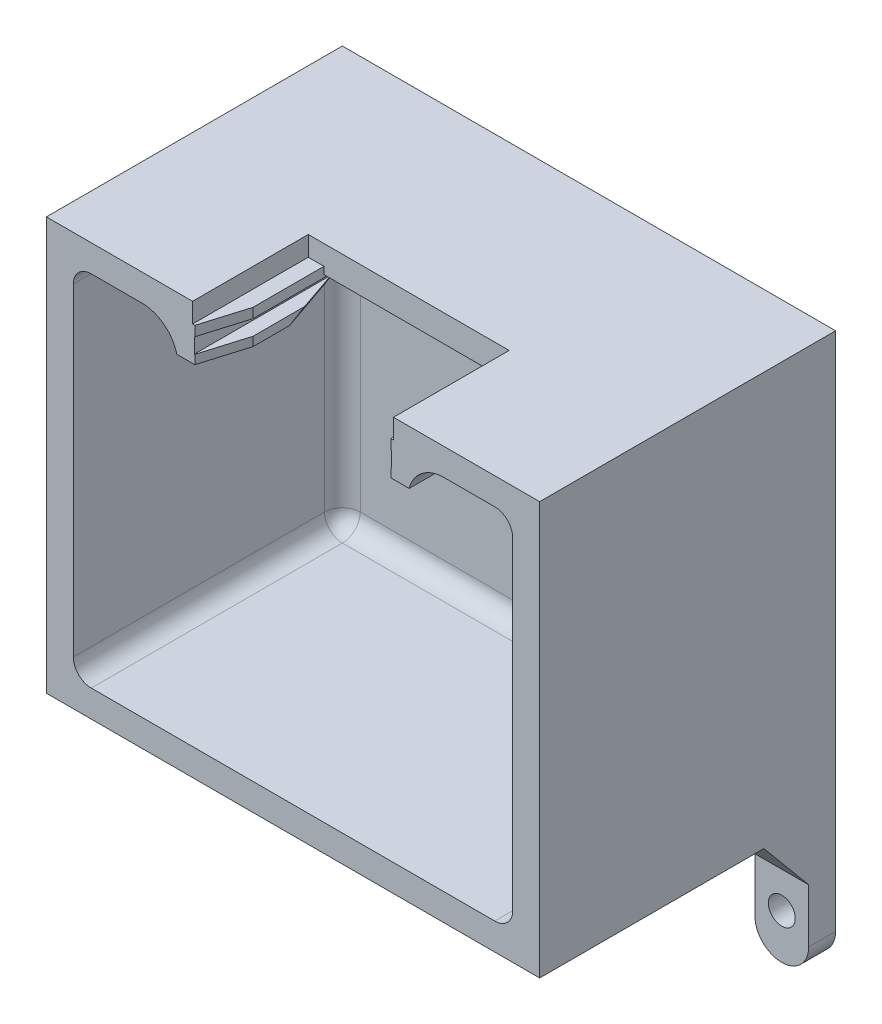
SolidWorks part; units mm, degrees
ref_plane "Front" through (0, 0, 0) normal (0, 0, 1) x (1, 0, 0)
ref_plane "Top" through (0, 0, 0) normal (0, 1, 0) x (1, 0, 0)
ref_plane "Right" through (0, 0, 0) normal (1, 0, 0) x (0, 0, -1)
sketch "Эскиз1" plane through (0, 0, 0) normal (0, 0, 1) x (1, 0, 0)
  line L0 (-27.5, -34) -> (-27.5, 40) construction
  line L1 (27.5, 43) -> (-27.5, 43)
  line L2 (27.5, 43) -> (27.5, -3)
  line L3 (21.5, -3) -> (-21.5, -3)
  line L4 (-27.5, 43) -> (-27.5, -3)
  line L5 (-27.5, 40) -> (27.5, 40) construction
  line L6 (8.25, 40) -> (-8.25, 40)
  line L7 (8.25, 40) -> (8.25, 30)
  line L8 (8.25, 30) -> (-8.25, 30)
  line L9 (-8.25, 40) -> (-8.25, 30)
  line L10 (-27.5, -3) -> (-27.5, -18)
  line L11 (-27.5, -18) -> (-21.5, -18)
  line L12 (-21.5, -42) -> (-21.5, -6) construction
  line L13 (-21.5, -18) -> (-21.5, -3)
  line L14 (27.5, -3) -> (27.5, -18)
  line L15 (27.5, -18) -> (21.5, -18)
  line L16 (21.5, -42) -> (21.5, -6) construction
  line L17 (21.5, -18) -> (21.5, -3)
  circle A0 centre (-24.5, -13) radius 1.5
  circle A1 centre (24.5, -13) radius 1.5
  point P13 (0, 30)
  point P33 (-24.5, -18)
  point P34 (24.5, -18)
  dimension "D4" = 3
  dimension "D1" = 16.5
  dimension "D2" = 10
  dimension "D3" = 15
  dimension "D5" = 5
  dimension "D6" = 46
extrude "Бобышка-Вытянуть1" add sketch "Эскиз1" along normal blind 3
sketch "Эскиз2" plane through (0, 0, 3) normal (0, 0, 1) x (1, 0, 0)
  line L0 (-27.5, 43) -> (27.5, 43)
  line L1 (27.5, 43) -> (27.5, -3)
  line L2 (27.5, -18) -> (27.5, 43) construction
  line L3 (27.5, -3) -> (-27.5, -3)
  line L4 (-27.5, 43) -> (-27.5, -18) construction
  line L5 (-27.5, -3) -> (-27.5, 43)
  line L6 (-24.5, 40) -> (24.5, 40)
  line L7 (24.5, 40) -> (24.5, 0)
  line L8 (24.5, 0) -> (-24.5, 0)
  line L9 (-24.5, 0) -> (-24.5, 40)
  dimension "D1" = 3
extrude "Бобышка-Вытянуть2" add sketch "Эскиз2" along normal blind 30
sketch "Эскиз3" plane through (0, 43, 0) normal (0, 1, 0) x (1, 0, 0)
  line L0 (27.5, -33) -> (-27.5, -33) construction
  line L1 (-11, -20.3) -> (11, -20.3)
  line L2 (-11, -20.3) -> (-11, -33)
  line L3 (-11, -33) -> (11, -33)
  line L4 (11, -20.3) -> (11, -33)
  line L5 (11, -33) -> (11, -20.3) construction
  line L6 (-11.2, -20.1) -> (11.2, -20.1)
  line L7 (11.2, -20.1) -> (11.2, -33.2)
  line L8 (-11.2, -33.2) -> (11.2, -33.2)
  line L9 (-11.2, -20.1) -> (-11.2, -33.2)
  dimension "D1" = 0.2
extrude "Вырез-Вытянуть1" cut sketch "Эскиз3" against normal blind 40 contours L6 L7 L8 L9
sketch "Эскиз4" plane through (0, 0, 20.1) normal (0, 0, 1) x (1, 0, 0)
  line L0 (9.25, 41) -> (11.2, 41)
  line L1 (11.2, 40) -> (11.2, 43) construction
  line L2 (11.2, 41) -> (11.2, 40)
  line L4 (9.25, 41) -> (9.25, 39.5) construction
  line L5 (9.25, 39.5) -> (9.25, 41)
  line L7 (11, 38) -> (9.45, 38)
  line L8 (9.45, 38) -> (9.45, 37)
  line L9 (9.45, 37) -> (12.95, 37)
  line L10 (12.95, 37) -> (12.95, 40)
  line L11 (24.5, 40) -> (11.2, 40) construction
  line L12 (12.95, 40) -> (11.2, 40)
  line L13 (11, 39.7) -> (9.45, 39.7)
  line L14 (9.45, 39.7) -> (9.45, 40.8)
  line L15 (9.45, 40.8) -> (11, 40.8)
  line L17 (11, 38) -> (11, 39.7)
  line L18 (11, 40.8) -> (11.2, 40.8)
  line L20 (11.2, 41) -> (11.2, 39.5) construction
  line L21 (11, 40.8) -> (11, 39.7) construction
  line L22 (0, 43) -> (0, 31.928) construction
  line L23 (9.25, 38.2) -> (10.75, 38.2) construction
  line L24 (-11.2, 43) -> (11.2, 43) construction
  line L25 (11.2, 39.5) -> (9.25, 39.5) construction
  line L26 (-11, 38) -> (-11, 39.7)
  line L27 (-9.45, 40.8) -> (-11, 40.8)
  line L28 (-9.45, 39.7) -> (-9.45, 40.8)
  line L29 (-11, 39.7) -> (-9.45, 39.7)
  line L30 (-12.95, 40) -> (-11.2, 40)
  line L31 (-12.95, 37) -> (-12.95, 40)
  line L32 (-9.45, 37) -> (-12.95, 37)
  line L33 (-9.45, 38) -> (-9.45, 37)
  line L34 (-11, 38) -> (-9.45, 38)
  line L35 (-9.25, 39.5) -> (-9.25, 41)
  line L36 (-11.2, 41) -> (-11.2, 40)
  line L37 (-9.25, 41) -> (-11.2, 41)
  line L38 (-11, 40.8) -> (-11.2, 40.8)
  line M18 (11.2, 40) -> (11.2, 43)
  line M21 (-11.2, 40) -> (11.2, 40)
  dimension "D2" = 0.2
  dimension "D3" = 1.5
  dimension "D4" = 3
  dimension "D5" = 3.5
  dimension "D1" = 0.2
extrude "Бобышка-Вытянуть3" add sketch "Эскиз4" along normal up to surface (12.9 mm away) and the other way blind 2 contours L18 L15 L14 M21 M18 | L17 L7 L8 L9 L10 L12 L14 L13 M21 | L27 L38 L36 L28 M21 | L34 L26 L29 L28 L30 L31 L32 L33 M21 region at (10.325, 40.4, 20.1) region at (11.5267, 38.3827, 20.1) region at (-10.325, 40.4, 20.1) region at (-11.5267, 38.3827, 20.1) up to face at (0, 27.1667, 33)
fillet "Скругление1" radius 4 2 edges at (-12.95, 40, 25.55) (12.95, 40, 25.55)
chamfer "Фаска1" distance 1.5 distance2 5 3 edges at (-9.45, 37.5, 33) (-9.45, 40.25, 33) (9.45, 37.5, 33) first distance on face at (0, 33.9044, 33)
chamfer "Фаска2" distance 5 distance2 1.5 1 edges at (9.45, 40.25, 33) first distance on face at (9.45, 40.1667, 23.7333)
chamfer "Фаска4" [suppressed] distance 3 angle 45
chamfer "Фаска3" distance 3 distance2 5 2 edges at (13.1365, 40, 18.1) (-13.1365, 40, 18.1) first distance on face at (11.1325, 38.7578, 18.1) first distance on face at (-11.1325, 38.7578, 18.1)
chamfer "Фаска5" distance 2 distance2 3 2 edges at (9.45, 37.5, 17.2667) (-9.45, 37.5, 17.2667) first distance on face at (11.1325, 38.7578, 15.1704) first distance on face at (-11.1325, 38.7578, 15.1704)
chamfer "Фаска6" distance 6 distance2 5 2 edges at (24.5, -3, 3) (-24.5, -3, 3) first distance on face at (26, -13, 3) first distance on face at (-23, -13, 3)
fillet "Скругление2" radius 3 4 edges at (27.5, -18, 1.5) (21.5, -18, 1.5) (-21.5, -18, 1.5) (-27.5, -18, 1.5)
fillet "Скругление3" radius 2 9 edges at (16.375, 40, 3) (-24.5, 0, 18) (-24.5, 40, 18) (-24.5, 20, 3) (-16.375, 40, 3) (0, 0, 3) (24.5, 20, 3) (24.5, 0, 18) (24.5, 40, 18)
